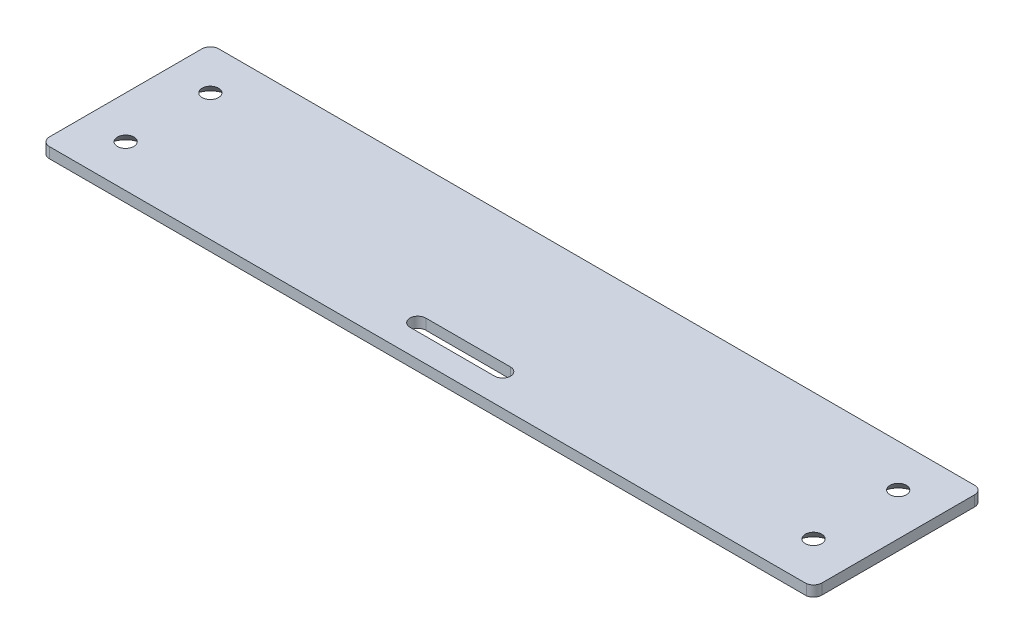
SolidWorks part; units mm, degrees
material "1060 Alloy"
ref_plane "Front Plane" through (0, 0, 0) normal (0, 0, 1) x (1, 0, 0)
ref_plane "Top Plane" through (0, 0, 0) normal (0, 1, 0) x (1, 0, 0)
ref_plane "Right Plane" through (0, 0, 0) normal (1, 0, 0) x (0, 0, -1)
sketch "Sketch1" plane through (0, 0, 0) normal (0, 1, 0) x (1, 0, 0)
  line L0 (22.1254, -125.5048) -> (-204.9255, -125.5048)
  line L1 (-207.4655, -228.2478) -> (-207.4655, 406.7522) construction
  line L3 (-207.4655, -128.0448) -> (-207.4655, -173.7648)
  line L6 (24.3095, -173.7899) -> (24.3095, -128.0198)
  line L9 (-204.9255, -176.3048) -> (22.1254, -176.3048)
  arc A2 (22.1254, -125.5048) -> (24.3095, -128.0198) centre (21.7695, -128.0198) cw
  arc A3 (22.1254, -176.3048) -> (24.3095, -173.7899) centre (21.7695, -173.7899) ccw
  arc A4 (-207.4655, -173.7648) -> (-204.9255, -176.3048) centre (-204.9255, -173.7648) ccw
  arc A5 (-207.4655, -128.0448) -> (-204.9255, -125.5048) centre (-204.9255, -128.0448) cw
  point P6 (-207.4655, -176.3048)
  point P13 (-207.4655, -125.5048)
  dimension "D1" = 2.54
  dimension "D2" = 2.54
  dimension "D3" = 2.54
  dimension "D4" = 2.54
  dimension "D5" = 231.775
extrude "Boss-Extrude1" add sketch "Sketch1" along normal blind 3.175
sketch "Sketch2" plane through (0, 0, 0) normal (0, -1, 0) x (1, 0, 0)
  line L0 (-194.7655, 150.9048) -> (-207.4655, 150.9048)
  line L2 (-194.7655, 150.9048) -> (-194.7655, 163.6048)
  line L3 (-194.7655, 150.9048) -> (-194.7655, 138.2048)
  line L4 (24.3095, 150.9048) -> (11.6095, 150.9048)
  line L5 (24.3095, 173.7899) -> (24.3095, 128.0198) construction
  line L6 (11.6095, 150.9048) -> (11.6095, 163.6048)
  line L7 (11.6095, 150.9048) -> (11.6095, 138.2048)
  line L8 (-207.4655, 128.0448) -> (-207.4655, 173.7648) construction
hole_wizard "#10 (0.1935) Diameter Hole1" positions "Sketch3" profile "Sketch4" hole size "#10" standard "ANSI Inch" end condition through all
sketch "Sketch3" plane through (0, 0, 0) normal (0, -1, 0) x (-1, 0, 0)
  point P0 (-11.6095, -163.6048)
  point P3 (-11.6095, -138.2048)
  point P6 (194.7655, -138.2048)
  point P9 (194.7655, -163.6048)
sketch "Sketch4" plane through (11.6095, 0, 163.6048) normal (1, 0, 0) x (0, 0, -1)
  line L0 (0, 0) -> (0, 3.175)
  line L1 (0, 3.175) -> (2.4574, 3.175)
  line L2 (2.4574, 3.175) -> (2.4574, 3.1776)
  line L3 (2.4574, 3.1776) -> (5.2197, 0)
  line L5 (5.2197, 0) -> (0, 0)
  line L6 (-2.4575, 3.1776) -> (-5.2197, 0) construction
  line L11 (0, -6.35) -> (0, 107.95) construction
  dimension "Thru Hole Dia." = 4.9149
  dimension "Thru Hole Depth" = 3.175
  dimension "Near C'Sink Dia." = 10.4394
  dimension "Near C'Sink Angle" = 82
sketch "Sketch6" plane through (0, 0, 0) normal (0, -1, 0) x (1, 0, 0)
  line L0 (-91.4001, 166.7798) -> (-91.4001, 176.3048) construction
  line L2 (-204.9255, 176.3048) -> (22.1254, 176.3048) construction
  line L3 (-78.878, 166.7798) -> (-103.9221, 166.7798) construction
  line L4 (-78.5221, 169.1674) -> (-103.9221, 169.1674)
  line L5 (-103.9221, 164.3922) -> (-78.5221, 164.3922)
  arc A0 (-103.9221, 169.1674) -> (-103.9221, 164.3922) centre (-103.9221, 166.7798) ccw
  arc A1 (-78.5221, 169.1674) -> (-78.5221, 164.3922) centre (-78.5221, 166.7798) cw
extrude "Cut-Extrude1" cut sketch "Sketch6" against normal blind 3.175
